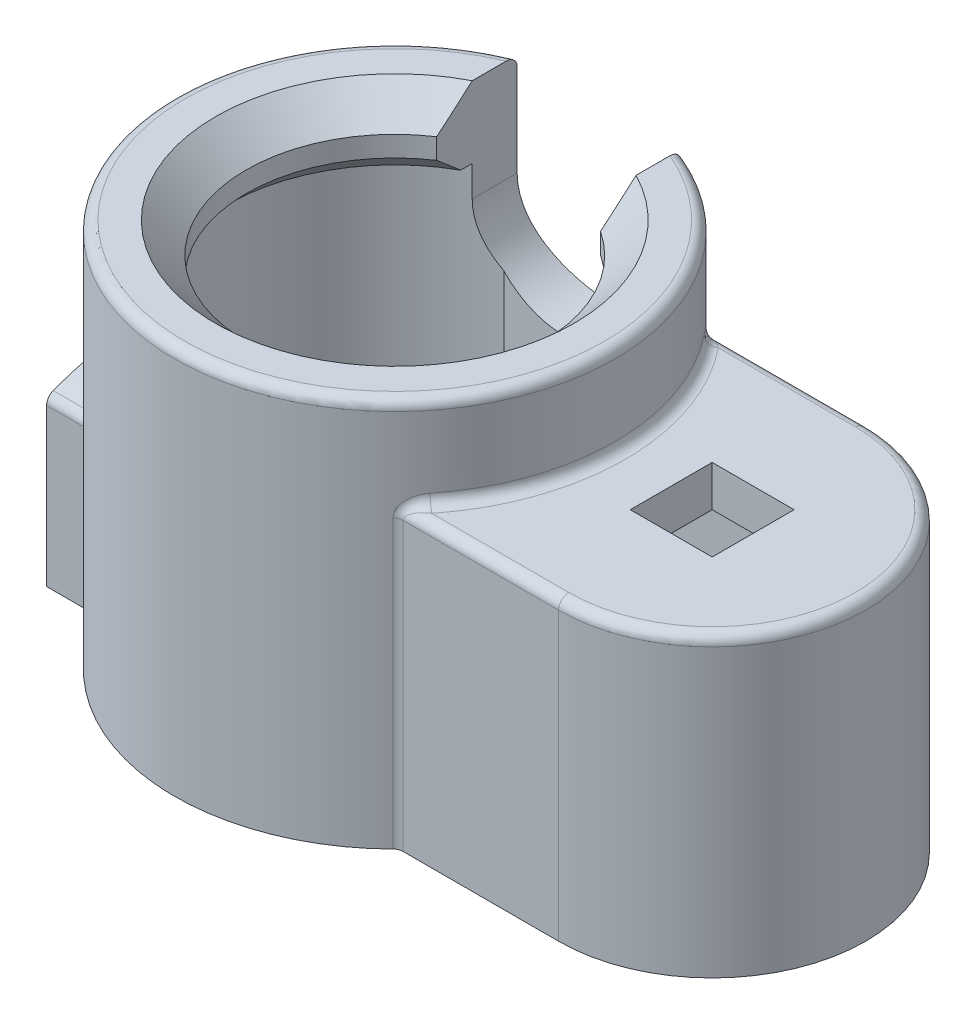
SolidWorks part; units mm, degrees
note: The reader was unsure of these and kept them because the rebuilt part matched: shared geometry of "草圖1<3>", "草圖2<3>".
ref_plane "前基準面" through (0, 0, 0) normal (0, 0, 1) x (1, 0, 0)
ref_plane "上基準面" through (0, 0, 0) normal (0, 1, 0) x (1, 0, 0)
ref_plane "右基準面" through (0, 0, 0) normal (1, 0, 0) x (0, 0, -1)
sketch "草圖1" plane through (0, 0, 0) normal (0, 1, 0) x (1, 0, 0)
  line L0 (15.4029, 15) -> (31, 15)
  line L1 (31, -15) -> (15.4029, -15)
  circle A0 centre (0, 0) radius 21.5
  arc A1 (31, 15) -> (31, -15) centre (31, 0) cw
  dimension "D1" = 15
  dimension "D2" = 43
  dimension "D3" = 31
extrude "伸長1" add sketch "草圖1" along normal blind 38
extrude "伸長2" add sketch "草圖1<3>" along normal blind 29 contours L1 A1 L0 A0
sketch "草圖1<3>" plane through (0, 0, 0) normal (0, 1, 0) x (1, 0, 0) same geometry as "草圖1"
sketch "草圖2" plane through (0, 0, 0) normal (0, -1, 0) x (1, 0, 0)
  line L0 (0, 0) -> (-11.1807, 0) construction
  line L1 (-5.831, 16.5) -> (5.831, 16.5)
  line L2 (-5.831, -16.5) -> (5.831, -16.5)
  line L7 (31, -11) -> (15.4029, -11)
  line L8 (15.4029, 11) -> (31, 11)
  line L9 (31, -11) -> (13.6107, -11)
  line L10 (13.6107, 11) -> (31, 11)
  arc A0 (5.831, -16.5) -> (5.831, 16.5) centre (0, 0) ccw
  arc A2 (-5.831, 16.5) -> (-5.831, -16.5) centre (0, 0) ccw
  arc A3 (31, -11) -> (31, 11) centre (31, 0) ccw
  arc A4 (31, -11) -> (31, 11) centre (31, 0) ccw
  dimension "D1" = 35
  dimension "D2" = 33
  dimension "D3" = 4
extrude "除料-伸長1" cut sketch "草圖2" against normal blind 31
extrude "除料-伸長2" cut sketch "草圖2<3>" against normal blind 25 contours L9 A4 L10 A0
sketch "草圖2<3>" plane through (0, 0, 0) normal (0, -1, 0) x (1, 0, 0) same geometry as "草圖2"
sketch "草圖3" plane through (0, 38, 0) normal (0, 1, 0) x (-1, 0, 0)
  circle A0 centre (0, 0) radius 14.5
  dimension "D1" = 29
extrude "除料-伸長3" cut sketch "草圖3" against normal up to next
chamfer "導角1" distance 3 angle 45 1 edges at (0, 38, 14.5)
chamfer "導角2" distance 2 angle 45 1 edges at (0, 31, -14.5)
fillet "圓角1" radius 1 10 edges at (15.4029, 14.5, -15) (15.4029, 14.5, 15) (21.5, 29, 0) (23.2015, 29, -15) (46, 29, 0) (23.2015, 29, 15) (0, 38, -21.5) (22.3053, 25, -11) (42, 25, 0) (22.3053, 25, 11)
ref_plane "平面1" through (-24, 0, 0) normal (1, 0, 0) x (0, 0, -1)
sketch "草圖4" plane through (-24, 0, 0) normal (1, 0, 0) x (0, 0, -1)
  line L0 (0, 0) -> (0, 25.3695) construction
  line L1 (-10, 16) -> (-10, 0)
  line L2 (-21.5, 0) -> (21.5, 0) construction
  line L3 (10, 16) -> (10, 0)
  line L4 (-10, 0) -> (10, 0)
  arc A0 (10, 16) -> (-10, 16) centre (0, -8) ccw
  dimension "D3" = 26
  dimension "D1" = 20
  dimension "D2" = 18
extrude "伸長3" add sketch "草圖4" along normal up to next
fillet "圓角2" radius 1 5 edges at (-19.0329, 8, -10) (-21.4488, 17.9576, -1.4836) (-19.0329, 8, 10) (-21.5164, 16, -10) (-21.5164, 16, 10)
sketch "草圖5" plane through (0, 0, 0) normal (0, 0, 1) x (1, 0, 0)
  line L0 (-33.2479, 10) -> (-2.2691, 10) construction
  line L1 (-24, 16) -> (-23, 16)
  line L2 (-24, 15.3238) -> (-24, 0) construction
  line L3 (-19.5, 12.5) -> (-19.5, 10)
  line L4 (-23, 16) -> (-19.5, 12.5)
  line L6 (-19.6278, 7.3722) -> (-22.4169, 4.5831) construction
  line L7 (-24, 16) -> (-24, 10)
  line L8 (-18.7554, 0) -> (15.1162, 0) construction
  line L9 (-19.6278, 0) -> (-19.6278, 15.3238) construction
  line L10 (-24, 10) -> (-19.5, 10)
  dimension "D1" = 1
  dimension "D2" = 90
  dimension "D3" = 5
  dimension "D4" = 12
  dimension "D5" = 10
revolve "除料-旋轉1" cut sketch "草圖5" angle 360 about L0
hole_wizard "M5 螺紋孔1" positions "草圖7" profile "草圖6" tap size "M5" standard "ISO"
sketch "草圖7" plane through (-19.5, 0, 0) normal (-1, 0, 0) x (0, 0, 1)
  point P0 (0, 10)
sketch "草圖6" plane through (-19.5, 10, 0) normal (0, 1, 0) x (0, 0, 1)
  line L0 (0, 0) -> (0, 2)
  line L1 (0, 2) -> (2.1, 2)
  line L2 (2.1, 2) -> (2.1, 0)
  line L5 (2.1, 0) -> (0, 0)
  line L11 (0, -6.35) -> (0, 107.95) construction
  dimension "貫穿螺孔鑽直徑" = 4.2
  dimension "貫穿螺孔鑽深度" = 2
cosmetic thread "鑽孔螺紋1" parameters "D2"=5
sketch "草圖8" plane through (0, 29, 0) normal (0, 1, 0) x (-1, 0, 0)
  line L0 (0, 0) -> (-27, 0) construction
  line L1 (-27, -4) -> (-35, -4)
  line L2 (-27, -4) -> (-27, 4)
  line L3 (-27, 4) -> (-35, 4)
  line L4 (-35, -4) -> (-35, 4)
  line L5 (-31, -4) -> (-31, 4) construction
  circle A0 centre (0, 0) radius 14.5 construction
  dimension "D1" = 8
  dimension "D2" = 31
extrude "除料-伸長4" cut sketch "草圖8" against normal through all
sketch "草圖9" plane through (0, 0, 0) normal (0, 0, 1) x (1, 0, 0)
  line L0 (20.5, 38) -> (-20.5, 38) construction
  line L1 (8, 38) -> (-8, 38)
  line L2 (-8, 38) -> (-8, 28)
  line L3 (8, 28) -> (8, 38)
  line L4 (17.5, 38) -> (-17.5, 38) construction
  arc A0 (-8, 28) -> (8, 28) centre (0, 28) ccw
  dimension "D1" = 8
  dimension "D2" = 10
extrude "除料-伸長5" cut sketch "草圖9" against normal through all
